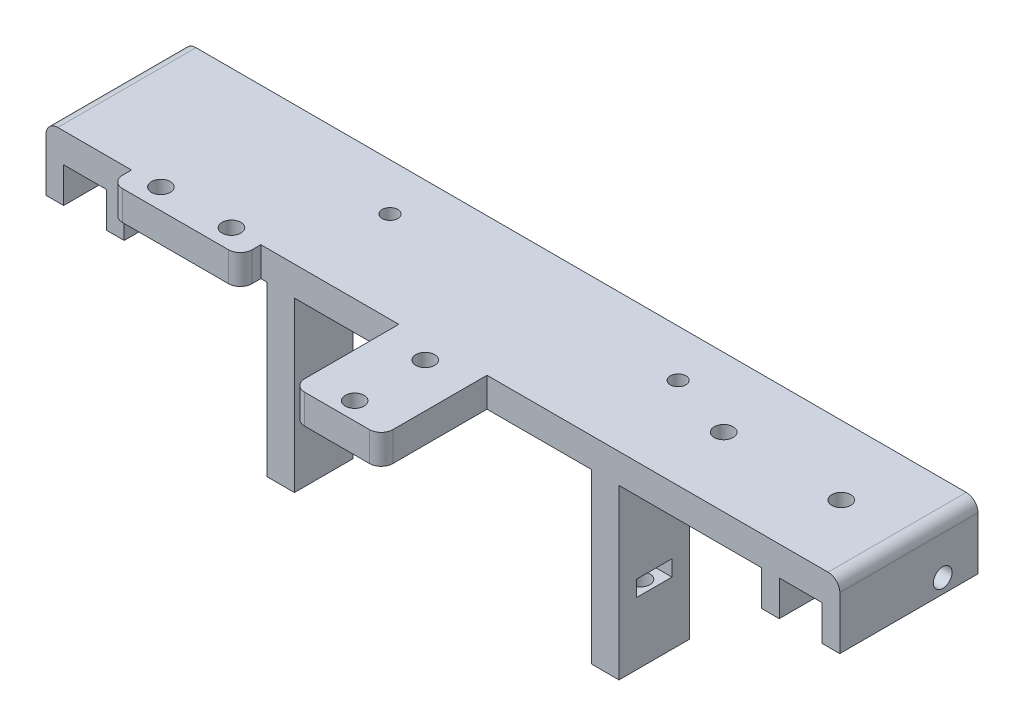
SolidWorks part; units mm, degrees
ref_plane "Front Plane" through (0, 0, 0) normal (0, 0, 1) x (1, 0, 0)
ref_plane "Top Plane" through (0, 0, 0) normal (0, 1, 0) x (1, 0, 0)
ref_plane "Right Plane" through (0, 0, 0) normal (1, 0, 0) x (0, 0, -1)
sketch "Sketch1" plane through (0, 0, 0) normal (0, 1, 0) x (1, 0, 0)
  line L0 (29.6, 67.5) -> (29.6, 0) construction
  line L1 (36.9, 40.198) -> (36.9, -24.324) construction
  line L2 (21.3575, 11.5) -> (46.1447, 11.5) construction
  line L3 (-26.9946, -2.6) -> (60.223, -2.6) construction
  line L4 (-27.6, 28.1106) -> (-27.6, -26.2389) construction
  line L5 (-92.1, 40.198) -> (-92.1, -24.324) construction
  line L6 (-76.5575, 11.5) -> (-101.3447, 11.5) construction
  line L7 (-84.8, 67.5) -> (-84.8, 0) construction
  line L8 (-27.6, 48.6658) -> (-27.6, 29.4209) construction
  line L9 (-42.1584, 38.5) -> (-13.0951, 38.5) construction
  circle A0 centre (0, 0) radius 1.6
  circle A1 centre (-55.2, 0) radius 1.6
  circle A2 centre (-52.1, 67.5) radius 1.3333
  circle A3 centre (-52.1, 9.5) radius 1.3333
  circle A4 centre (-3.1, 67.5) radius 1.3333
  circle A5 centre (-3.1, 9.5) radius 1.3333
  circle A6 centre (-27.6, -9) radius 1.6
  circle A7 centre (-27.6, -21) radius 1.6
  dimension "D1" = 3.2
  dimension "D8" = 2.6667
  dimension "D12" = 3.2
  dimension "D13" = 12
  dimension "D11" = 3.2
  dimension "D2" = 29.6
  dimension "D3" = 7.3
  dimension "D4" = 56
  dimension "D5" = 2.6
  dimension "D6" = 27.6
  dimension "D7" = 67.5
  dimension "D9" = 29
  dimension "D10" = 24.5
  dimension "D14" = 9
ref_axis "Axis1" through (21.3575, 0, -11.5) along (1, 0, 0)
sketch "Sketch3" plane through (0, 0, 0) normal (0, 1, 0) x (1, 0, 0)
  line L0 (-92.1, 40.198) -> (-92.1, -24.324) construction
  line L1 (-95.1, 17.5) -> (39.9, 17.5)
  line L2 (-95.1, 17.5) -> (-95.1, -6)
  line L3 (-95.1, -6) -> (39.9, -6)
  line L4 (39.9, 17.5) -> (39.9, -6)
  line L5 (36.9, 40.198) -> (36.9, -24.324) construction
  line L6 (-76.5575, 11.5) -> (-101.3447, 11.5) construction
  line L7 (-27.6, 28.1106) -> (-27.6, -26.2389) construction
  line L8 (-20.1, -24) -> (-35.1, -24)
  line L9 (-20.1, -24) -> (-20.1, -6)
  line L10 (-20.1, -6) -> (-35.1, -6)
  line L11 (-35.1, -24) -> (-35.1, -6)
  line L12 (-20.1, -24) -> (-35.1, -6) construction
  line L13 (-20.1, -6) -> (-35.1, -24) construction
  line L14 (-95.1, 5.75) -> (39.9, 5.75) construction
  line L15 (-52.1, 9.5) -> (-95.1, 9.5) construction
  line L16 (18.4, 9.5) -> (18.4, -30.1908) construction
  line L17 (-3.1, 9.5) -> (39.9, 9.5) construction
  line L18 (-69.5608, 9.5) -> (-69.5608, -14.0047) construction
  line L20 (-80.5608, -9.5) -> (-58.5608, -9.5)
  line L21 (-80.5608, -9.5) -> (-80.5608, -6)
  line L22 (-80.5608, -6) -> (-58.5608, -6)
  line L23 (-58.5608, -9.5) -> (-58.5608, -6)
  line L24 (-80.5608, -9.5) -> (-58.5608, -6) construction
  line L25 (-80.5608, -6) -> (-58.5608, -9.5) construction
  circle A0 centre (-27.6, -9) radius 1.6 construction
  circle A1 centre (-27.6, -21) radius 1.6 construction
  circle A2 centre (-27.6, -9) radius 1.6
  circle A3 centre (-27.6, -21) radius 1.6
  circle A4 centre (8.4, 5.75) radius 1.6
  circle A5 centre (28.4, 5.75) radius 1.6
  circle A6 centre (-75.5608, -6) radius 1.6
  circle A7 centre (-63.5608, -6) radius 1.6
  point P11 (-27.6, -15)
  point P44 (-69.5608, -7.75)
  dimension "D7" = 3.2
  dimension "D8" = 10
  dimension "D10" = 3.2
  dimension "D1" = 3
  dimension "D2" = 3
  dimension "D3" = 6
  dimension "D4" = 6
  dimension "D5" = 18
  dimension "D6" = 15
  dimension "D9" = 6
  dimension "D11" = 3.5
  dimension "D12" = 5
extrude "Boss-Extrude1" add sketch "Sketch3" along normal blind 5 contours L4 L1 L2 L3 | L11 L8 L9 L3 A3 A2 | L3 A7 A6 L21 L20 L23 region at (-27.7278, 0, -5.7783) region at (-69.5608, 0, 7.8749) region at (-27.6, 0, 15)
sketch "Sketch4" plane through (0, 0, 0) normal (0, -1, 0) x (1, 0, 0)
  line L0 (36.9, -40.198) -> (36.9, 24.324) construction
  line L1 (39.9, 6) -> (36.9, 6)
  line L2 (39.9, 6) -> (39.9, -17.5)
  line L3 (39.9, -17.5) -> (36.9, -17.5)
  line L4 (36.9, 6) -> (36.9, -17.5)
  line L6 (29.6, -67.5) -> (29.6, 0) construction
  line L7 (29.6, 6) -> (26.6, 6)
  line L8 (29.6, 6) -> (29.6, -17.5)
  line L9 (29.6, -17.5) -> (26.6, -17.5)
  line L10 (26.6, 6) -> (26.6, -17.5)
  line L12 (-92.1, -40.198) -> (-92.1, 24.324) construction
  line L13 (-95.1, 6) -> (-92.1, 6)
  line L14 (-95.1, 6) -> (-95.1, -17.5)
  line L15 (-95.1, -17.5) -> (-92.1, -17.5)
  line L16 (-92.1, 6) -> (-92.1, -17.5)
  line L17 (-84.8, -67.5) -> (-84.8, 0) construction
  line L18 (-84.8, -17.5) -> (-81.8, -17.5)
  line L19 (-84.8, -17.5) -> (-84.8, 6)
  line L20 (-84.8, 6) -> (-81.8, 6)
  line L21 (-81.8, -17.5) -> (-81.8, 6)
  line L22 (-58.5608, 6) -> (-35.1, 6) construction
  line L23 (-95.1, -17.5) -> (39.9, -17.5) construction
  line L24 (-20.1, 6) -> (39.9, 6) construction
  dimension "D1" = 3
  dimension "D2" = 3
  dimension "D3" = 3
extrude "Boss-Extrude2" add sketch "Sketch4" along normal blind 6
sketch "Sketch5" plane through (39.9, 0, 0) normal (1, 0, 0) x (0, 0, -1)
  line L0 (11.5, 0) -> (11.5, -8.447) construction
  line L1 (67.5, 0) -> (0, 0) construction
  line L3 (40.198, 0) -> (-24.324, 0) construction
  line L4 (40.198, 0) -> (-24.324, 0)
  circle A0 centre (11.5, -3.55) radius 1.6
  point P4 (11.5, 0)
  dimension "D1" = 3.2
  dimension "D2" = 3.55
extrude "Cut-Extrude1" cut sketch "Sketch5" against normal through all contours A0
sketch "Sketch6" plane through (0, 0, 0) normal (0, -1, 0) x (1, 0, 0)
  line L1 (-57.55, -6) -> (-52.85, -6)
  line L2 (-57.55, -6) -> (-57.55, 6)
  line L3 (-57.55, 6) -> (-52.85, 6)
  line L4 (-52.85, -6) -> (-52.85, 6)
  line L5 (-57.55, -6) -> (-52.85, 6) construction
  line L6 (-57.55, 6) -> (-52.85, -6) construction
  line L8 (-2.35, -6) -> (2.35, -6)
  line L9 (-2.35, -6) -> (-2.35, 6)
  line L10 (-2.35, 6) -> (2.35, 6)
  line L11 (2.35, -6) -> (2.35, 6)
  line L12 (-2.35, -6) -> (2.35, 6) construction
  line L13 (-2.35, 6) -> (2.35, -6) construction
  circle A0 centre (-55.2, 0) radius 1.6 construction
  circle A1 centre (-55.2, 0) radius 1.6
  circle A2 centre (0, 0) radius 1.6 construction
  circle A3 centre (0, 0) radius 1.6
  point P1 (-55.2, 0)
  dimension "D2" = 50.5
extrude "Boss-Extrude3" add sketch "Sketch6" along normal blind 28.65
sketch "Sketch8" plane through (-57.55, 0, 0) normal (-1, 0, 0) x (0, 0, 1)
  line L0 (-1.6, -28.65) -> (1.6, -28.65) construction
  line L1 (-1.6, -28.65) -> (1.6, -28.65)
  line L2 (0, -28.65) -> (0, -11.1841) construction
  line L4 (-3, -15.3) -> (3, -15.3)
  line L5 (-3, -15.3) -> (-3, -18)
  line L6 (-3, -18) -> (3, -18)
  line L7 (3, -15.3) -> (3, -18)
  line L8 (-3, -15.3) -> (3, -18) construction
  line L9 (-3, -18) -> (3, -15.3) construction
  point P5 (0, -16.65)
  dimension "D1" = 6
  dimension "D2" = 2.7
  dimension "D3" = 12
extrude "Cut-Extrude3" cut sketch "Sketch8" against normal through all contours L7 L4 L5 L6 region at (-57.55, -16.65, 0)
fillet "Fillet1" radius 2 2 edges at (39.9, 5, -5.75) (-95.1, 5, -5.75)
chamfer "Chamfer1" distance 2 angle 45 2 edges at (-2.35, -14.325, -6) (-52.85, -14.325, -6)
sketch "Sketch9" plane through (0, 0, 0) normal (0, 1, 0) x (1, 0, 0)
  circle A0 centre (-3.1, 9.5) radius 1.3333 construction
  circle A1 centre (-52.1, 9.5) radius 1.3333 construction
  circle A2 centre (-3.1, 9.5) radius 1.3333
  circle A3 centre (-52.1, 9.5) radius 1.3333
extrude "Cut-Extrude4" cut sketch "Sketch9" along normal blind 25
sketch "Sketch10" plane through (0, 0, 0) normal (0, -1, 0) x (1, 0, 0)
  line L1 (-60.4051, 5.0662) -> (-61.1743, 8.266)
  line L2 (-61.1743, 8.266) -> (-64.3299, 9.1998)
  line L3 (-64.3299, 9.1998) -> (-66.7164, 6.9338)
  line L4 (-66.7164, 6.9338) -> (-65.9473, 3.734)
  line L5 (-65.9473, 3.734) -> (-62.7916, 2.8002)
  line L6 (-62.7916, 2.8002) -> (-60.4051, 5.0662)
  line L7 (-75.8952, 9.2739) -> (-78.5633, 7.3473)
  line L8 (-78.5633, 7.3473) -> (-78.2288, 4.0734)
  line L9 (-78.2288, 4.0734) -> (-75.2263, 2.7261)
  line L10 (-75.2263, 2.7261) -> (-72.5583, 4.6527)
  line L11 (-72.5583, 4.6527) -> (-72.8928, 7.9266)
  line L12 (-72.8928, 7.9266) -> (-75.8952, 9.2739)
  circle A0 centre (-63.5608, 6) radius 2.85 construction
  circle A1 centre (-75.5608, 6) radius 2.85 construction
  dimension "D1" = 5.7
  dimension "D2" = 5.7
fillet "Fillet2" radius 2 4 edges at (-20.1, 2.5, 24) (-35.1, 2.5, 24) (-80.5608, 2.5, 9.5) (-58.5608, 2.5, 9.5)
equation "\"D2@Sketch4\"=\"D1@Sketch4\""
equation "\"D3@Sketch4\"=\"D1@Sketch4\""
